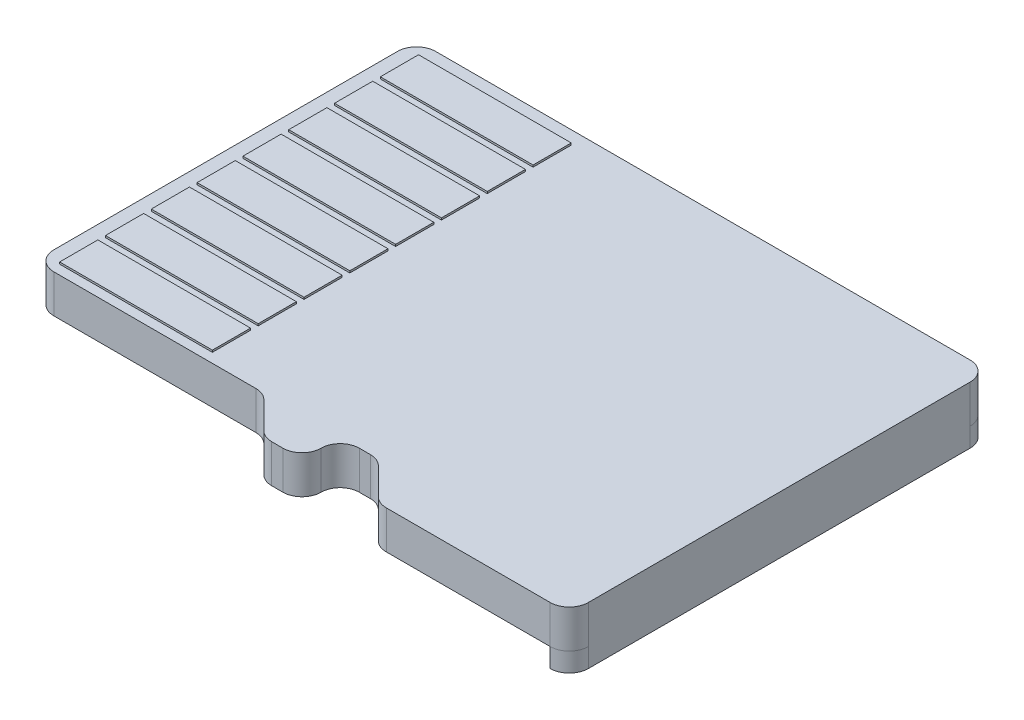
SolidWorks part; units mm, degrees
material "ABS"
ref_plane "Front Plane" through (0, 0, 0) normal (0, 0, 1) x (1, 0, 0)
ref_plane "Top Plane" through (0, 0, 0) normal (0, 1, 0) x (1, 0, 0)
ref_plane "Right Plane" through (0, 0, 0) normal (1, 0, 0) x (0, 0, -1)
sketch "Sketch1" plane through (0, 0, 0) normal (0, 1, 0) x (1, 0, 0)
  line L1 (-7.5, 5) -> (7.5, 5)
  line L2 (-7.5, 5) -> (-7.5, -5)
  line L3 (-7.5, -5) -> (7.5, -5)
  line L4 (7.5, 5) -> (7.5, -5)
  line L5 (-7.5, 5) -> (7.5, -5) construction
  line L6 (-7.5, -5) -> (7.5, 5) construction
  point P0 (0, 0)
  dimension "D1" = 15
  dimension "D2" = 10
extrude "Boss-Extrude1" add sketch "Sketch1" along normal blind 1
sketch "Sketch2" plane through (0, 1, 0) normal (0, 1, 0) x (1, 0, 0)
  line L0 (7.5, -5) -> (7.5, -6)
  line L1 (7.5, -6) -> (2.5, -6)
  line L5 (2.5, -6) -> (1.5, -5)
  line L6 (1.5, -5) -> (7.5, -5)
  dimension "D3" = 6
  dimension "D1" = 1
  dimension "D2" = 5
extrude "Boss-Extrude2" add sketch "Sketch2" against normal blind 1
sketch "Sketch3" plane through (0, 1, 0) normal (0, 1, 0) x (1, 0, 0)
  line L0 (0.5, -5) -> (0.5, -6)
  line L1 (-7.5, -5) -> (1.5, -5) construction
  line L2 (0.5, -6) -> (-0.5, -6)
  line L5 (7.5, -6) -> (7.5, 5) construction
  line L6 (-0.5, -6) -> (-1.5, -5)
  line L7 (-1.5, -5) -> (0.5, -5)
  dimension "D1" = 1
  dimension "D2" = 7
  dimension "D3" = 2
  dimension "D4" = 1
extrude "Boss-Extrude3" add sketch "Sketch3" against normal blind 1
sketch "Sketch4" plane through (0, 1, 0) normal (0, 1, 0) x (1, 0, 0)
  line L0 (-7.5, -5) -> (-1.5, -5) construction
  line L5 (-7.0982, -3.75) -> (-3.0982, -3.75)
  line L6 (-7.0982, -3.75) -> (-7.0982, -4.75)
  line L7 (-7.0982, -4.75) -> (-3.0982, -4.75)
  line L8 (-3.0982, -3.75) -> (-3.0982, -4.75)
  dimension "D1" = 4
  dimension "D2" = 1
  dimension "D3" = 0.25
extrude "Boss-Extrude4" add sketch "Sketch4" along normal blind 0.05
pattern_linear "LPattern1" count 8 spacing 1.2 along (0, 0, -1) of "Boss-Extrude4"
fillet "Fillet1" radius 0.5 10 edges at (-1.5, 0.5, 5) (1.5, 0.5, 5) (0.5, 0.5, 5) (2.5, 0.5, 6) (-0.5, 0.5, 6) (0.5, 0.5, 6) (7.5, 0.5, 6) (7.5, 0.5, -5) (-7.5, 0.5, -5) (-7.5, 0.5, 5)
sketch "Sketch6" plane through (0, 0, 0) normal (0, -1, 0) x (1, 0, 0)
  line L0 (7.5, -5) -> (7.5, 6)
  line L1 (7.5, 6) -> (7, 6)
  line L2 (7.5, -5) -> (7, -5)
  line L3 (7.5, 5.5) -> (7.5, -4.5) construction
  arc A0 (7, 6) -> (7, -5) centre (22.8552, 0.5) ccw
extrude "Boss-Extrude5" add sketch "Sketch6" along normal blind 0.5
fillet "Fillet2" radius 0.5 2 edges at (7.5, -0.25, 6) (7.5, -0.25, -5)
